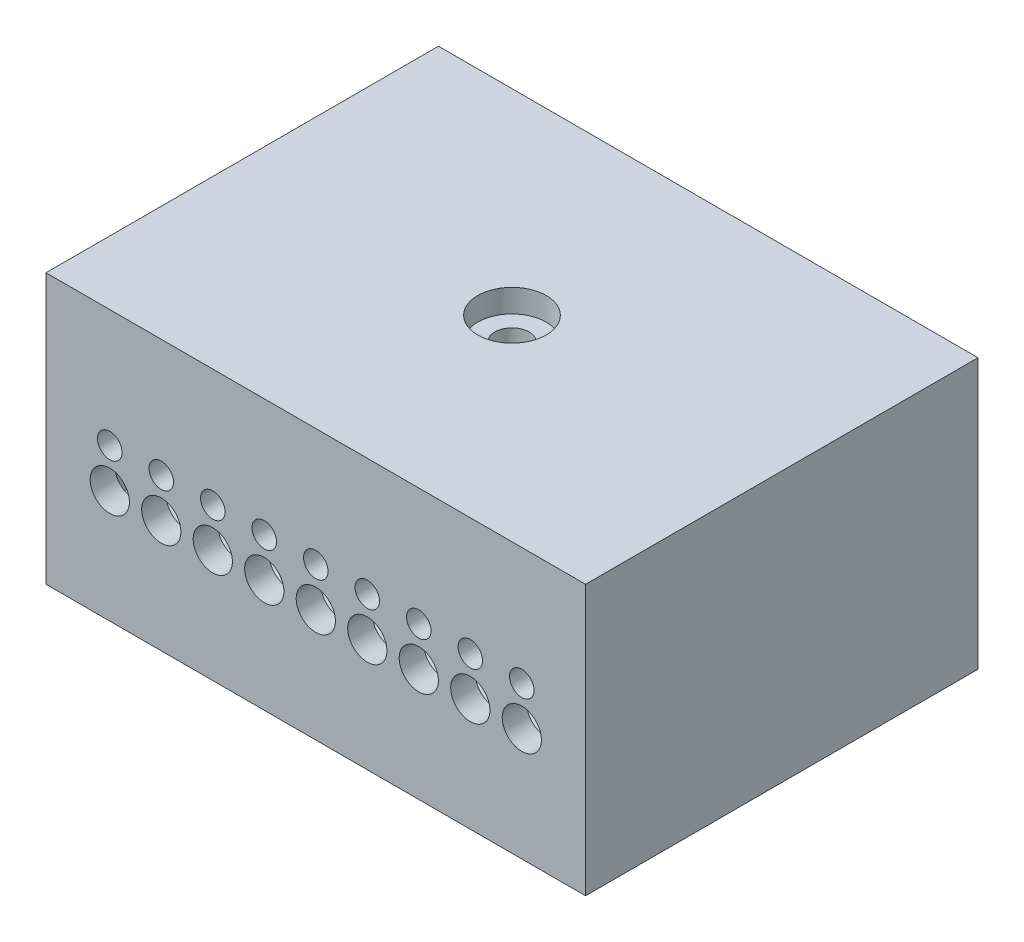
SolidWorks part; units mm, degrees
ref_plane "Front Plane" through (0, 0, 0) normal (0, 0, 1) x (1, 0, 0)
ref_plane "Top Plane" through (0, 0, 0) normal (0, 1, 0) x (1, 0, 0)
ref_plane "Right Plane" through (0, 0, 0) normal (1, 0, 0) x (0, 0, -1)
sketch "Sketch2" plane through (0, 0, 0) normal (0, 0, 1) x (1, 0, 0)
  line L1 (0, 0) -> (110, 0)
  line L2 (0, 0) -> (0, 55)
  line L3 (0, 55) -> (110, 55)
  line L4 (110, 0) -> (110, 55)
  line L5 (0, 0) -> (110, 55) construction
  line L6 (0, 55) -> (110, 0) construction
  point P4 (55, 27.5)
  dimension "D1" = 110
  dimension "D2" = 55
extrude "Boss-Extrude1" add sketch "Sketch2" along normal blind 80
sketch "Sketch3" plane through (0, 0, 0) normal (0, -1, 0) x (1, 0, 0)
  line L0 (0, 80) -> (110, 0) construction
  line L1 (10, 70) -> (100, 70)
  line L2 (10, 70) -> (10, 10)
  line L3 (10, 10) -> (100, 10)
  line L4 (100, 70) -> (100, 10)
  line L5 (10, 70) -> (100, 10) construction
  line L6 (10, 10) -> (100, 70) construction
  line L7 (110, 80) -> (0, 0) construction
  line L8 (0, 80) -> (0, 0) construction
  line L9 (0, 0) -> (110, 0) construction
  point P4 (55, 40)
  point P13 (0, 0)
  dimension "D1" = 10
  dimension "D2" = 10
ref_plane "Plane1" through (0, 10, 0) normal (0, -1, 0) x (-1, 0, 0)
sketch "Sketch4" plane through (0, 10, 0) normal (0, -1, 0) x (-1, 0, 0)
  line L4 (-100, -70) -> (-10, -70)
  line L5 (-100, -10) -> (-100, -70)
  line L6 (-10, -10) -> (-100, -10)
  line L7 (-10, -70) -> (-10, -10)
  line L8 (-100, -70) -> (-10, -70)
  line L9 (-100, -10) -> (-100, -70)
  line L10 (-10, -10) -> (-100, -10)
  line L11 (-10, -70) -> (-10, -10)
  dimension "D1" = 0
extrude "Cut-Extrude2" cut sketch "Sketch4" along normal blind 10 draft 20 draft outward yes
hole_wizard "CBORE for M6 Hex Head Machine Screw1" positions "Sketch7" profile "Sketch6" counterbore size "M6" standard "ANSI Metric" end condition through all
sketch "Sketch7" plane through (0, 55, 0) normal (0, 1, 0) x (1, 0, 0)
  line L1 (0, 0) -> (110, -80) construction
  line L2 (110, 0) -> (0, -80) construction
  point P0 (55, -40)
  point P14 (0, 0)
sketch "Sketch6" plane through (55, 55, 40) normal (1, 0, 0) x (0, 0, 1)
  line L0 (0, 0) -> (0, 55)
  line L1 (0, 55) -> (3.5, 55)
  line L3 (3.5, 55) -> (3.5, 4.7)
  line L4 (3.5, 4.7) -> (6.975, 4.7)
  line L5 (6.975, 4.7) -> (6.975, 0)
  line L7 (6.975, 0) -> (0, 0)
  line L11 (0, -6.35) -> (0, 107.95) construction
  dimension "Thru Hole Dia." = 7
  dimension "Thru Hole Depth" = 55
  dimension "C'Bore Dia." = 13.95
  dimension "C'Bore Depth" = 4.7
shell "Shell4" thickness 5 removed face at (55, 27.5, 0)
sketch "Sketch8" plane through (0, 0, 75) normal (0, 0, -1) x (-1, 0, 0)
  line L0 (-105, 5) -> (-105, 50) construction
  line L1 (-6.499, 15) -> (-103.501, 15) construction
  line L2 (-55, 50) -> (-55, 14.6488) construction
  line L6 (-105, 50) -> (-5, 50) construction
  circle A0 centre (-97, 31) radius 2.5
  circle A1 centre (-97, 23) radius 4
  circle A2 centre (-86.5, 31) radius 2.5
  circle A3 centre (-86.5, 23) radius 4
  circle A4 centre (-76, 31) radius 2.5
  circle A5 centre (-76, 23) radius 4
  circle A6 centre (-65.5, 31) radius 2.5
  circle A7 centre (-65.5, 23) radius 4
  circle A8 centre (-55, 31) radius 2.5
  circle A9 centre (-55, 23) radius 4
  circle A10 centre (-44.5, 31) radius 2.5
  circle A11 centre (-44.5, 23) radius 4
  circle A12 centre (-34, 31) radius 2.5
  circle A13 centre (-34, 23) radius 4
  circle A14 centre (-23.5, 31) radius 2.5
  circle A15 centre (-23.5, 23) radius 4
  circle A16 centre (-13, 31) radius 2.5
  circle A17 centre (-13, 23) radius 4
  point P44 (0, 0)
  dimension "D1" = 5
  dimension "D2" = 8
  dimension "D3" = 8
  dimension "D4" = 8
  dimension "D5" = 8
  dimension "D6" = 9
extrude "Cut-Extrude4" cut sketch "Sketch8" against normal up to next
equation "\"D2@Sketch2\"=\"D1@Sketch2\"/2"
equation "\"D1@Boss-Extrude1\"=\"D1@Sketch2\"-30"
